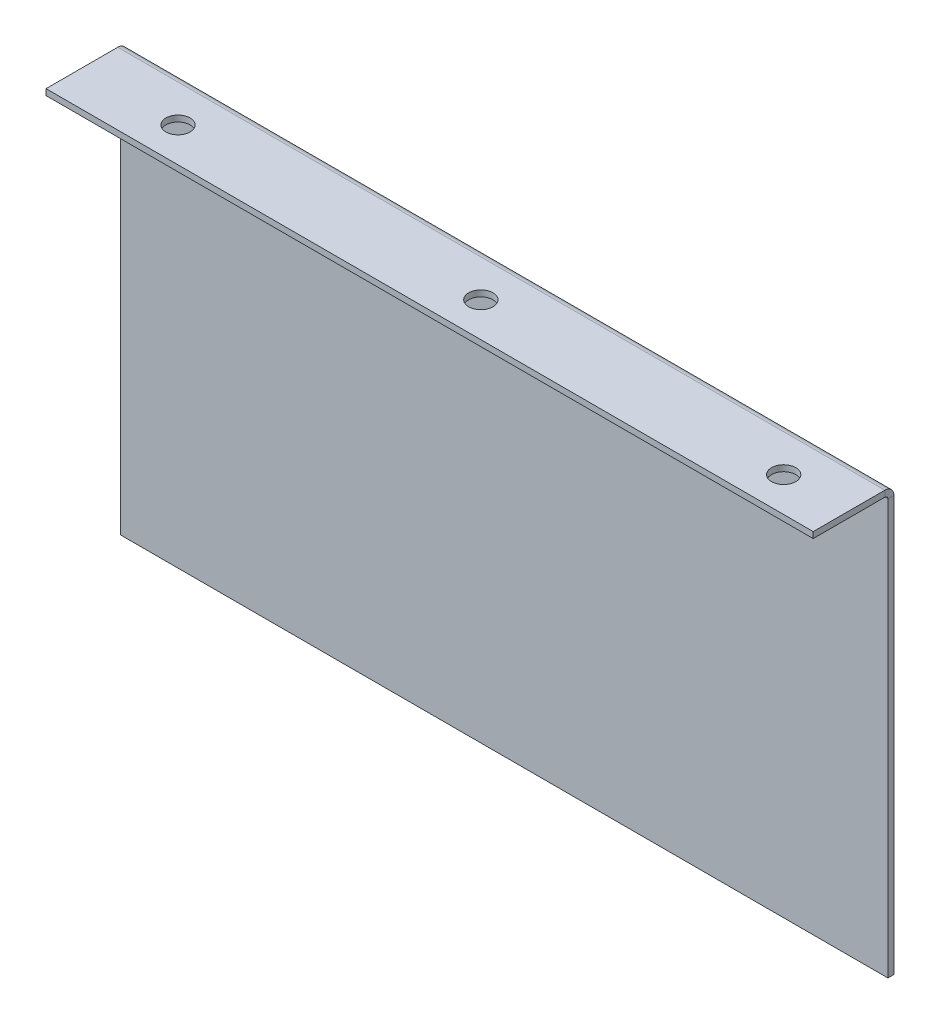
SolidWorks part; units mm, degrees
note: The reader was unsure of these and kept them because the rebuilt part matched: flange length of "Edge-Flange1".
ref_plane "Front Plane" through (0, 0, 0) normal (0, 0, 1) x (1, 0, 0)
ref_plane "Top Plane" through (0, 0, 0) normal (0, 1, 0) x (1, 0, 0)
ref_plane "Right Plane" through (0, 0, 0) normal (1, 0, 0) x (0, 0, -1)
sketch "Sketch1" plane through (0, 0, 0) normal (0, 0, 1) x (1, 0, 0)
  line L1 (-102.1053, 48.7719) -> (87.8947, 48.7719)
  line L2 (-102.1053, 48.7719) -> (-102.1053, -56.2281)
  line L3 (-102.1053, -56.2281) -> (87.8947, -56.2281)
  line L4 (87.8947, 48.7719) -> (87.8947, -56.2281)
  dimension "D1" = 190
  dimension "D2" = 105
base flange "Base-Flange1" sketch "Sketch1" thickness 1.5 reverse thickness direction no parameters "D1"=0.7366
edge flange "Edge-Flange1" sketch "Sketch8" flange angle 90 flange length 20 flange position material inside bend radius 0.7366 thickness 1.5 relief rectangular parameters "D6"=10
sketch "Sketch8" plane through (0, 48.7719, 0) normal (0, 1, 0) x (-1, 0, 0)
  line L0 (-87.8947, 0) -> (102.1053, 0) construction
  line L1 (-87.8947, 0) -> (102.1053, 0)
  line L2 (-87.8947, 0) -> (-87.8947, 18.5)
  line L3 (-87.8947, 18.5) -> (102.1053, 18.5)
  line L4 (102.1053, 18.5) -> (102.1053, 0)
bend "EdgeBend1" bend radius 0.7366 bend angle 90 parameters "D5"=1
sketch "Sketch9" plane through (0, 47.2719, 0) normal (0, -1, 0) x (1, 0, 0)
  circle A0 centre (-77.978, 9.9464) radius 3.005
extrude "Cut-Extrude1" cut sketch "Sketch9" against normal blind 10 normal cut yes
pattern_linear "LPattern1" count 3 spacing 75 along (1, 0, 0) of "Cut-Extrude1"
sketch "Bend-Lines1" [suppressed] plane through (0, 0, 0) normal (0, 1, 0) x (1, 0, 0)
sketch "Bounding-Box1" [suppressed] plane through (0, 0, 0) normal (0, 1, 0) x (1, 0, 0)
sheet metal parameters "Sheet-Metal1" thickness 1.5 parameters "D1"=0.7366
flat pattern "Flat-Pattern1" [suppressed]
sketch "Bend-Lines2" plane through (0, 0, 0) normal (0, 1, 0) x (1, 0, 0)
sketch3d "Bounding-Box2" [suppressed]
  line L0 (102.1053, -56.2281, 0) -> (-87.8947, -56.2281, 0) construction
  line L1 (102.1053, 48.7719, 0) -> (-87.8947, 48.7719, 0) construction
  line L2 (102.1053, -56.2281, 0) -> (102.1053, 48.7719, 0) construction
  line L3 (-87.8947, -56.2281, 0) -> (-87.8947, 48.7719, 0) construction
sheet metal parameters "Sheet-Metal2" thickness 1.5 parameters "D1"=0.7366
flat pattern "Flat-Pattern1"
sketch "Bend-Lines2" plane through (0, 0, 0) normal (0, 0, 1) x (1, 0, 0)
  line L0 (87.8947, 47.7029) -> (-102.1053, 47.7029) construction
  line L1 (87.8947, 47.7029) -> (-102.1053, 47.7029) construction
sketch3d "Bounding-Box2" [suppressed]
  line L0 (-102.1053, -56.2281, 0) -> (87.8947, -56.2281, 0) construction
  line L1 (-102.1053, 66.6339, 0) -> (87.8947, 66.6339, 0) construction
  line L2 (-102.1053, -56.2281, 0) -> (-102.1053, 66.6339, 0) construction
  line L3 (87.8947, -56.2281, 0) -> (87.8947, 66.6339, 0) construction
bend of the flat pattern "Flatten-<EdgeBend1>1"
sheet metal parameters "Sheet-Metal3" thickness 1.5 parameters "D1"=0.7366
flat pattern "Flat-Pattern1"
sketch "Bend-Lines2" plane through (0, 0, 0) normal (0, 0, 1) x (1, 0, 0)
  line L0 (87.8947, 47.7029) -> (-102.1053, 47.7029) construction
  line L1 (87.8947, 47.7029) -> (-102.1053, 47.7029) construction
sketch3d "Bounding-Box2" [suppressed]
  line L0 (-102.1053, -56.2281, 0) -> (87.8947, -56.2281, 0) construction
  line L1 (-102.1053, 66.6339, 0) -> (87.8947, 66.6339, 0) construction
  line L2 (-102.1053, -56.2281, 0) -> (-102.1053, 66.6339, 0) construction
  line L3 (87.8947, -56.2281, 0) -> (87.8947, 66.6339, 0) construction
bend of the flat pattern "Flatten-<EdgeBend1>1"
sheet metal parameters "Sheet-Metal4" thickness 1.5 parameters "D1"=0.7366
flat pattern "Flat-Pattern1"
sketch "Bend-Lines2" plane through (0, 0, 0) normal (0, 0, 1) x (1, 0, 0)
  line L0 (87.8947, 47.7029) -> (-102.1053, 47.7029) construction
  line L1 (87.8947, 47.7029) -> (-102.1053, 47.7029) construction
sketch3d "Bounding-Box2" [suppressed]
  line L0 (-102.1053, -56.2281, 0) -> (87.8947, -56.2281, 0) construction
  line L1 (-102.1053, 66.6339, 0) -> (87.8947, 66.6339, 0) construction
  line L2 (-102.1053, -56.2281, 0) -> (-102.1053, 66.6339, 0) construction
  line L3 (87.8947, -56.2281, 0) -> (87.8947, 66.6339, 0) construction
bend of the flat pattern "Flatten-<EdgeBend1>1"
